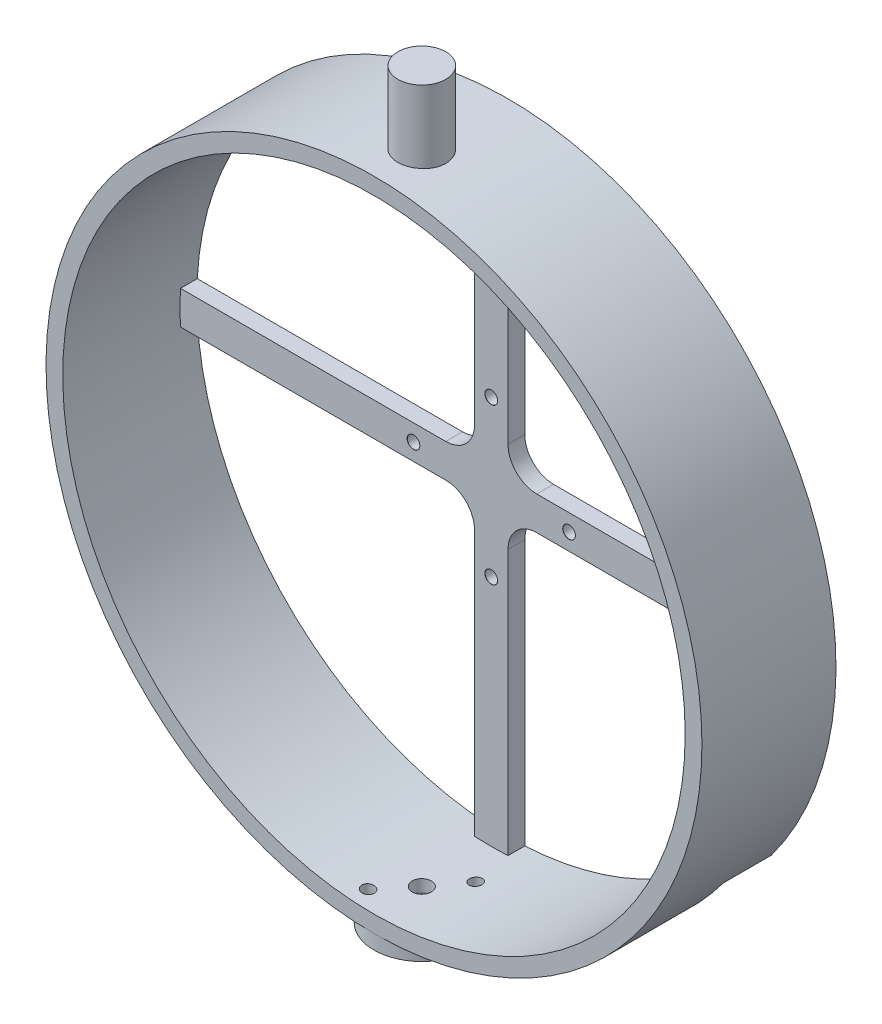
SolidWorks part; units mm, degrees
ref_plane "Plan de face" through (0, 0, 0) normal (0, 0, 1) x (1, 0, 0)
ref_plane "Plan de dessus" through (0, 0, 0) normal (0, 1, 0) x (1, 0, 0)
ref_plane "Plan de droite" through (0, 0, 0) normal (1, 0, 0) x (0, 0, -1)
sketch "Esquisse1" plane through (0, 0, 0) normal (0, 0, 1) x (1, 0, 0)
  circle A0 centre (0, 0) radius 65
  circle A1 centre (0, 0) radius 68.5
  dimension "D1" = 130
  dimension "D2" = 3.5
extrude "Boss.-Extru.1" add sketch "Esquisse1" along normal blind 28
sketch "Esquisse2" plane through (0, 0, 0) normal (0, 0, -1) x (-1, 0, 0)
  line L0 (0, 65) -> (0, 3.5) construction
  line L1 (-65, 0) -> (65, 0) construction
  line L2 (-3.5, 64.9057) -> (-3.5, 9.5)
  line L3 (-64.9057, -3.5) -> (-9.5, -3.5)
  line L4 (3.5, 64.9057) -> (3.5, 9.5)
  line L5 (-64.9057, 3.5) -> (-9.5, 3.5)
  line L6 (-3.5, 65) -> (-3.5, -65) construction
  line L7 (3.5, 65) -> (3.5, -65) construction
  line L8 (-65, 3.5) -> (65, 3.5) construction
  line L9 (-65, -3.5) -> (65, -3.5) construction
  line L10 (9.5, 3.5) -> (64.9057, 3.5)
  line L11 (0, 0) -> (0, -65) construction
  line L12 (0, 65) -> (0, -65) construction
  line L13 (-3.5, -9.5) -> (-3.5, -64.9057)
  line L14 (3.5, -9.5) -> (3.5, -64.9057)
  line L15 (9.5, -3.5) -> (64.9057, -3.5)
  circle A0 centre (0, 0) radius 65 construction
  arc A1 (-64.9057, 3.5) -> (-64.9057, -3.5) centre (0, 0) ccw
  arc A2 (-9.5, -3.5) -> (-3.5, -9.5) centre (-9.5, -9.5) cw
  arc A3 (3.5, -9.5) -> (9.5, -3.5) centre (9.5, -9.5) cw
  arc A4 (9.5, 3.5) -> (3.5, 9.5) centre (9.5, 9.5) cw
  arc A5 (-9.5, 3.5) -> (-3.5, 9.5) centre (-9.5, 9.5) ccw
  arc A6 (3.5, 64.9057) -> (-3.5, 64.9057) centre (0, 0) ccw
  arc A7 (64.9057, -3.5) -> (64.9057, 3.5) centre (0, 0) ccw
  arc A8 (-3.5, -64.9057) -> (3.5, -64.9057) centre (0, 0) ccw
  point P33 (3.5, -3.5)
  dimension "D3" = 6
  dimension "D1" = 3.5
  dimension "D2" = 3.5
extrude "Boss.-Extru.2" add sketch "Esquisse2" against normal blind 3.5
sketch "Esquisse3" plane through (0, 0, 0) normal (1, 0, 0) x (0, 0, -1)
  line L0 (0, 68.5) -> (-28, 68.5) construction
  line L1 (0, 68.5) -> (-13, 68.5)
  line L2 (-28, -68.5) -> (0, -68.5) construction
  line L3 (-8, -68.5) -> (0, -68.5)
  line L4 (-18, -71.5) -> (-18, 84.9317) construction
  line L7 (-18, -71.5) -> (-8, -71.5)
  line L8 (-8, -68.5) -> (-8, -71.5)
  line L9 (-18, -71.5) -> (-18, -68.5)
  line L11 (-18, 68.5) -> (-18, 83.5)
  line L12 (-18, 83.5) -> (-13, 83.5)
  line L13 (-13, 68.5) -> (-13, 83.5)
  line L14 (-18, 68.5) -> (-28, 68.5)
  line L15 (-28, 68.5) -> (-28, -68.5) construction
  line L17 (-18, 68.5) -> (-18, 67.5)
  line L18 (-18, 67.5) -> (-13, 67.5)
  line L19 (-13, 68.5) -> (-13, 67.5)
  line L21 (-8, -68.5) -> (-8, -67.5)
  line L22 (-8, -67.5) -> (-18, -67.5)
  line L23 (-18, -68.5) -> (-18, -67.5)
  point P9 (-18, 68.5)
  dimension "D1" = 1
  dimension "D2" = 1
  dimension "D3" = 5
  dimension "D4" = 15
  dimension "D5" = 10
  dimension "D6" = 10
revolve "Révolution1" add sketch "Esquisse3" angle 360 about L4 region at (0, -69.5, 13) region at (0, 75.5, 15.5)
sketch "Esquisse4" plane through (0, -71.5, 0) normal (0, -1, 0) x (1, 0, 0)
  point P0 (4.9505, 11.7157)
  point P1 (-4.9505, 24.2843)
hole_wizard "Dégagement M21" positions "Esquisse4" profile "Esquisse5" hole size "M2" standard "ISO"
sketch "Esquisse5" plane through (4.9505, -71.5, 11.7157) normal (1, 0, 0) x (0, 0, -1)
  line L0 (0, 0) -> (0, 10.7811)
  line L1 (0, 10.7811) -> (1.3, 10)
  line L2 (1.3, 10) -> (1.3, 0.025)
  line L3 (1.3, 0.025) -> (1.325, 0)
  line L5 (1.325, 0) -> (0, 0)
  line L6 (-1.3, 0.025) -> (-1.325, 0) construction
  line L10 (0, 10.7811) -> (-1.3, 10) construction
  line L11 (0, -6.35) -> (0, 107.95) construction
  dimension "Diamètre du perçage" = 2.6
  dimension "Profondeur du perçage" = 10
  dimension "Diamètre du fraisage entrant" = 2.65
  dimension "Angle du fraisage entrant" = 90
  dimension "Angle de pointe" = 118
sketch "Esquisse6" plane through (0, -71.5, 0) normal (0, -1, 0) x (1, 0, 0)
  point P0 (0, 18)
hole_wizard "Dégagement M22" positions "Esquisse6" profile "Esquisse7" hole size "M2" standard "ISO"
sketch "Esquisse7" plane through (0, -71.5, 18) normal (1, 0, 0) x (0, 0, -1)
  line L0 (0, 0) -> (0, 10.7811)
  line L1 (0, 10.7811) -> (1.3, 10)
  line L2 (1.3, 10) -> (1.3, 0.025)
  line L3 (1.3, 0.025) -> (1.325, 0)
  line L5 (1.325, 0) -> (0, 0)
  line L6 (-1.3, 0.025) -> (-1.325, 0) construction
  line L10 (0, 10.7811) -> (-1.3, 10) construction
  line L11 (0, -6.35) -> (0, 107.95) construction
  dimension "Diamètre du perçage" = 2.6
  dimension "Profondeur du perçage" = 10
  dimension "Diamètre du fraisage entrant" = 2.65
  dimension "Angle du fraisage entrant" = 90
  dimension "Angle de pointe" = 118
ref_plane "Plan1" through (0, -65, 0) normal (0, 1, 0) x (1, 0, 0)
sketch "Esquisse8" plane through (0, -65, 0) normal (0, 1, 0) x (1, 0, 0)
  circle A0 centre (0, -18) radius 2
  dimension "D1" = 4
extrude "Enlèv. mat.-Extru.2" cut sketch "Esquisse8" against normal blind 3.5 and the other way blind 10
ref_plane "Plan2" through (48.4368, -48.4368, 0) normal (0.7071, -0.7071, 0) x (0, 0, -1)
sketch "Esquisse9" plane through (48.4368, -48.4368, 0) normal (0.7071, -0.7071, 0) x (0, 0, -1)
  line L1 (-10, -10) -> (10, -10)
  line L2 (-10, -10) -> (-10, 10)
  line L3 (-10, 10) -> (10, 10)
  line L4 (10, -10) -> (10, 10)
  line L5 (-10, -10) -> (10, 10) construction
  line L6 (-10, 10) -> (10, -10) construction
  point P0 (0, 0)
  dimension "D1" = 20
  dimension "D2" = 20
extrude "Enlèv. mat.-Extru.4" cut sketch "Esquisse9" against normal blind 13.5 and the other way blind 13.5 contours L2 L1 L4 L3
sketch "Esquisse10" plane through (0, 0, 3.5) normal (0, 0, 1) x (1, 0, 0)
  point P0 (-16.25, 0)
  point P1 (0, 16.25)
  point P3 (16.25, 0)
  point P5 (0, -16.25)
hole_wizard "Dégagement M23" positions "Esquisse10" profile "Esquisse11" hole size "M2" standard "ISO"
sketch "Esquisse11" plane through (-16.25, 0, 3.5) normal (1, 0, 0) x (0, -1, 0)
  line L0 (0, 0) -> (0, 10.7811)
  line L1 (0, 10.7811) -> (1.3, 10)
  line L2 (1.3, 10) -> (1.3, 0.025)
  line L3 (1.3, 0.025) -> (1.325, 0)
  line L5 (1.325, 0) -> (0, 0)
  line L6 (-1.3, 0.025) -> (-1.325, 0) construction
  line L10 (0, 10.7811) -> (-1.3, 10) construction
  line L11 (0, -6.35) -> (0, 107.95) construction
  dimension "Diamètre du perçage" = 2.6
  dimension "Profondeur du perçage" = 10
  dimension "Diamètre du fraisage entrant" = 2.65
  dimension "Angle du fraisage entrant" = 90
  dimension "Angle de pointe" = 118
